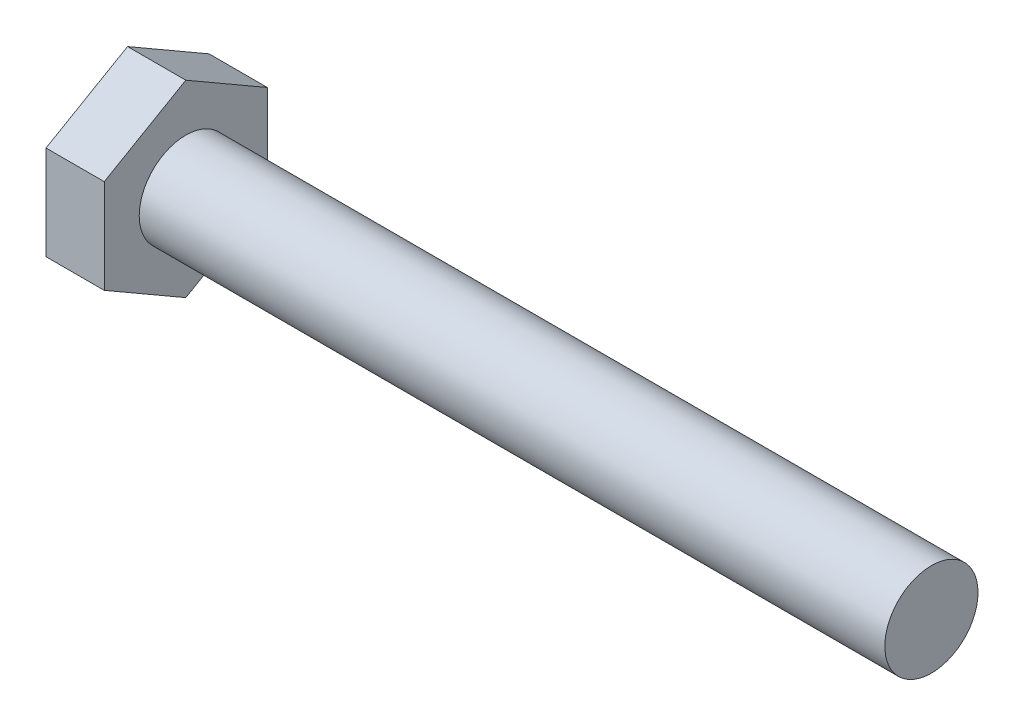
SolidWorks part; units mm, degrees
material "AISI 4130 Steel, normalized at 870C"
ref_plane "Front Plane" through (0, 0, 0) normal (0, 0, 1) x (1, 0, 0)
ref_plane "Top Plane" through (0, 0, 0) normal (0, 1, 0) x (1, 0, 0)
ref_plane "Right Plane" through (0, 0, 0) normal (1, 0, 0) x (0, 0, -1)
sketch "Sketch1" plane through (0, 0, 0) normal (0, 0, 1) x (1, 0, 0)
  line L0 (-27.3844, 0) -> (27.3844, 0) construction
  line L1 (27.3844, 3.175) -> (27.3844, -3.175) construction
  line L2 (-23.4156, 5.5562) -> (-23.4156, -5.5562) construction
  line L3 (-27.3844, 5.5562) -> (-27.3844, -5.5562) construction
  point P9 (-23.4156, 0)
  point P10 (22.9394, -3.175)
  point P11 (8.3344, 0)
  dimension "Screw Dia" = 6.35
  dimension "Hex" = 11.1125
  dimension "Head Ht" = 3.9688
  dimension "Screw Length" = 50.8
  dimension "D1" = 4.445
  dimension "Thread Length" = 19.05
ref_plane "Plane2" through (27.3844, 0, 0) normal (1, 0, 0) x (0, 0, -1)
sketch "Sketch5" plane through (27.3844, 0, 0) normal (1, 0, 0) x (0, 0, -1)
  circle A0 centre (0, 0) radius 3.175
extrude "Boss-Extrude3" add sketch "Sketch5" against normal up to vertex (50.8 mm away) up to point (-23.4156, 0, 0)
sketch "Sketch9" [suppressed] plane through (27.3844, 0, 0) normal (1, 0, 0) x (0, 0, -1)
  circle A1 centre (0, 0) radius 3.175
  circle A2 centre (0, 0) radius 3.175
  dimension "D1" = 0
chamfer "Chamfer1" [suppressed] distance 0.9525 angle 45
sketch "Sketch11" plane through (0, 0, 0) normal (0, 0, 1) x (1, 0, 0)
  line L0 (-23.4156, 3.175) -> (-23.4156, 0)
  line L1 (-23.4156, 0) -> (11.5094, 0)
  line L3 (11.5094, 0) -> (8.3344, 3.175)
  line L4 (-23.4156, 3.175) -> (8.3344, 3.175)
  dimension "D1" = 45
  dimension "MIn Thread" = 19.05
revolve "Revolve1" add sketch "Sketch11" angle 360 about L1
sketch "Sketch6" plane through (-23.4156, 0, 0) normal (-1, 0, 0) x (0, 0, 1)
  line L0 (0, 5.5562) -> (0, -5.5562) construction
  line L1 (5.5563, 3.2079) -> (0, 6.4158)
  line L2 (0, 6.4158) -> (-5.5562, 3.2079)
  line L3 (-5.5562, 3.2079) -> (-5.5562, -3.2079)
  line L4 (-5.5562, -3.2079) -> (0, -6.4158)
  line L5 (0, -6.4158) -> (5.5563, -3.2079)
  line L6 (5.5563, -3.2079) -> (5.5563, 3.2079)
  circle A0 centre (0, 0) radius 5.5562 construction
extrude "Boss-Extrude4" add sketch "Sketch6" along normal up to vertex (3.9688 mm away) up to point (-27.3844, -5.5562, 0)
sketch "Sketch7" plane through (-27.3844, 0, 0) normal (-1, 0, 0) x (0, 0, 1)
  circle A0 centre (0, 0) radius 5.5562 construction
  circle A1 centre (0, 0) radius 5.5562
sketch "Sketch8" plane through (-27.3844, 0, 0) normal (-1, 0, 0) x (0, 0, 1)
  circle A0 centre (0, 0) radius 5.5562 construction
  circle A1 centre (0, 0) radius 5.5562
extrude "Cut-Extrude3" [suppressed] cut sketch "Sketch8" against normal through all draft 60 flip side to cut
sketch "Sketch12" plane through (-27.3844, 0, 0) normal (-1, 0, 0) x (0, 0, 1)
  line L0 (0, 4.2783) -> (0, 2.3892) construction
  line L1 (0.1667, 4.2783) -> (0.1667, 2.3892)
  line L2 (-0.1667, 4.2783) -> (-0.1667, 2.3892)
  line L3 (0, 3.175) -> (0, -3.175) construction
  arc A0 (0.1667, 4.2783) -> (-0.1667, 4.2783) centre (0, 4.2783) ccw
  arc A1 (-0.1667, 2.3892) -> (0.1667, 2.3892) centre (0, 2.3892) ccw
  circle A3 centre (0, 0) radius 2.2225 construction
  circle A4 centre (0, 0) radius 4.445 construction
  point P2 (0, 3.3337)
  dimension "D1" = 4.445
  dimension "D3" = 8.89
  dimension "D2" = 0.3334
extrude "Cut-Extrude4" [suppressed] cut sketch "Sketch12" against normal blind 0.254
pattern_circular "CirPattern1" [suppressed] count 6 over 360 of bodies 116
ref_plane "Plane3" through (8.3344, 0, 0) normal (1, 0, 0) x (0, 0, -1)
split "Split1" [suppressed] bodies to split 117
curve "Helix/Spiral1" [suppressed] pitch 1.27 height 20.32 turns 16 parameters "Pitch"=1.27
sketch "Sketch10" [suppressed] plane through (0, 0, 0) normal (0, 0, 1) x (1, 0, 0)
  line L0 (27.3844, 3.175) -> (27.8606, 2.3501)
  line L1 (27.8606, 2.3501) -> (28.0194, 2.3501)
  line L2 (28.0194, 2.3501) -> (28.4956, 3.175)
  line L3 (27.3844, 3.175) -> (28.4956, 3.175)
  line L4 (27.94, 3.175) -> (27.94, 2.3501) construction
  line L5 (27.6225, 2.7626) -> (28.2575, 2.7626) construction
  dimension "D1" = 60
  dimension "D2" = 0.1588
  dimension "D3" = 0.635
sweep "Cut-Sweep1" [suppressed] cut profiles "Sketch10" path "Helix/Spiral1"
sketch "Sketch13" [suppressed] plane through (8.3344, 0, 0) normal (1, 0, 0) x (0, 0, -1)
  circle A1 centre (0, 0) radius 3.175
  circle A2 centre (0, 0) radius 3.175
  dimension "D1" = 0
extrude "Boss-Extrude5" [suppressed] add sketch "Sketch13" along normal through all draft 60
equation "\"D2@Sketch10\" = \"Pitch@Helix/Spiral1\"*.125"
equation "\"D3@Sketch10\" = \"Pitch@Helix/Spiral1\"*.5"
equation "\"D3@Helix/Spiral1\"=\"Thread Length@Sketch1\"+\"Pitch@Helix/Spiral1\""
equation "\"D1@Chamfer1\" = \"Pitch@Helix/Spiral1\"*.75"
equation "\"D1@Sketch12\" = \"Hex@Sketch1\"*.4"
equation "\"D3@Sketch12\" = \"Hex@Sketch1\"*.8"
equation "\"D2@Sketch12\" = \"Hex@Sketch1\"*.03"
equation "\"D1@Sketch1\" = \"Pitch@Helix/Spiral1\"*3.5"
